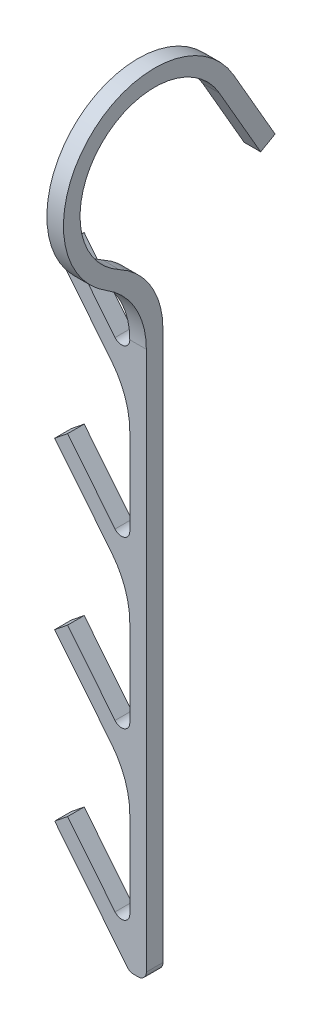
SolidWorks part; units mm, degrees
ref_plane "Front Plane" through (0, 0, 0) normal (0, 0, 1) x (1, 0, 0)
ref_plane "Top Plane" through (0, 0, 0) normal (0, 1, 0) x (1, 0, 0)
ref_plane "Right Plane" through (0, 0, 0) normal (1, 0, 0) x (0, 0, -1)
sketch "Sketch1" plane through (0, 0, 0) normal (1, 0, 0) x (0, 0, -1)
  circle A2 centre (0, 0) radius 22
  circle A3 centre (0, 0) radius 18
  dimension "D1" = 44
  dimension "D2" = 4
extrude "Boss-Extrude1" add sketch "Sketch1" along normal blind 4
sketch "Sketch2" plane through (4, 0, 0) normal (1, 0, 0) x (0, 0, -1)
  line L0 (19.0526, 11) -> (29.0526, -6.3205)
  line L1 (29.0526, -6.3205) -> (25.5885, -8.3205)
  line L2 (25.5885, -8.3205) -> (15.5885, 9)
  line L3 (15.5885, 9) -> (19.0526, 11)
  line L4 (0, 0) -> (0, 18) construction
  circle A0 centre (0, 0) radius 22 construction
  circle A1 centre (0, 0) radius 18 construction
  dimension "D1" = 20
  dimension "D2" = 30
extrude "Boss-Extrude2" add sketch "Sketch2" against normal up to surface (4 mm away) up to face at (0, 0, -22)
sketch "Sketch3" plane through (4, 0, 0) normal (1, 0, 0) x (0, 0, -1)
  line L0 (4.6587, -17.3867) -> (5.694, -21.2504)
  line L1 (0, 0) -> (0, -22) construction
  line L2 (21.913, -1.9545) -> (15.5885, 9)
  line L3 (21.913, -1.9545) -> (25.5885, -8.3205) construction
  circle A0 centre (0, 0) radius 18
  circle A1 centre (0, 0) radius 22
  circle A2 centre (0, 0) radius 18 construction
  arc A3 (19.0526, 11) -> (21.913, -1.9545) centre (0, 0) ccw construction
  circle M6 centre (0, 0) radius 18
  arc M8 (19.0526, 11) -> (21.913, -1.9545) centre (0, 0) ccw
  dimension "D1" = 15
extrude "Cut-Extrude1" cut sketch "Sketch3" against normal through all contours L2 L0 M8 M6 region at (4, -10.4169, -15.0287)
sketch "Sketch4" plane through (4, 0, 0) normal (1, 0, 0) x (0, 0, -1)
  line L1 (-2, -17.8885) -> (2, -17.8885)
  line L2 (-2, -17.8885) -> (-2, -47.8885)
  line L3 (-2, -47.8885) -> (2, -47.8885)
  line L4 (2, -17.8885) -> (2, -47.8885)
  arc A0 (15.5885, 9) -> (4.6587, -17.3867) centre (0, 0) ccw construction
  point P7 (0, -17.8885)
  dimension "D1" = 4
  dimension "D2" = 30
extrude "Boss-Extrude3" add sketch "Sketch4" against normal up to surface (4 mm away) up to face at (0, -1.442, -6.6971)
sketch "Sketch5" plane through (4, 0, 0) normal (1, 0, 0) x (0, 0, -1)
  line L0 (2, -21.9089) -> (2, -17.8885)
  line L1 (2, -17.8885) -> (4.6587, -17.3867)
  line L2 (4.6587, -17.3867) -> (5.694, -21.2504)
  arc A0 (2, -21.9089) -> (5.694, -21.2504) centre (2, -11.2189) ccw
extrude "Cut-Extrude2" cut sketch "Sketch5" against normal through all
fillet "Fillet1" radius 20 2 edges at (2, -17.8885, -2) (2, -21.9089, 2)
fillet "Fillet2" radius 20 1 edges at (2, -17.8885, 2)
sketch "Sketch6" plane through (0, 0, 0) normal (-1, 0, 0) x (0, 0, 1)
  line L0 (-2, -47.8885) -> (2, -47.8885) construction
  line L1 (-2, -47.8885) -> (2, -47.8885)
  line L2 (-2, -47.8885) -> (-2, -167.8885)
  line L3 (-2, -167.8885) -> (2, -167.8885)
  line L4 (2, -47.8885) -> (2, -167.8885)
  point P4 (0, -47.8885)
  point P7 (0, -47.8885)
  dimension "D1" = 120
  dimension "D2" = 4
extrude "Boss-Extrude4" add sketch "Sketch6" against normal up to surface (4 mm away) up to face at (4, -15.5959, -3.8329)
sketch "Sketch7" plane through (0, 0, 2) normal (0, 0, 1) x (1, 0, 0)
  line L0 (0, -167.8885) -> (-18.1152, -145.3977)
  line L1 (0, -167.8885) -> (0, -35.7771) construction
  line L2 (-18.1152, -145.3977) -> (-15, -142.8885)
  line L3 (-15, -142.8885) -> (0, -161.5118)
  line L4 (0, -161.5118) -> (0, -167.8885)
  line L5 (0, -121.5118) -> (0, -127.8885)
  line L6 (0, -127.8885) -> (-18.1152, -105.3977)
  line L7 (-18.1152, -105.3977) -> (-15, -102.8885)
  line L8 (-15, -102.8885) -> (0, -121.5118)
  line L9 (0, -81.5118) -> (0, -87.8885)
  line L10 (0, -87.8885) -> (-18.1152, -65.3977)
  line L11 (-18.1152, -65.3977) -> (-15, -62.8885)
  line L12 (-15, -62.8885) -> (0, -81.5118)
  line L13 (0, -41.5118) -> (0, -47.8885)
  line L14 (0, -47.8885) -> (-18.1152, -25.3977)
  line L15 (-18.1152, -25.3977) -> (-15, -22.8885)
  line L16 (-15, -22.8885) -> (0, -41.5118)
  dimension "D1" = 4
  dimension "D2" = 15
  dimension "D3" = 25
  dimension "D5" = 33.6232
  dimension "D4" = 4
extrude "Boss-Extrude5" add sketch "Sketch7" against normal up to surface (4 mm away) up to face at (2, -100.6775, -2)
fillet "Fillet3" radius 20 3 edges at (0, -127.8885, 0) (0, -87.8885, 0) (0, -47.8885, 0)
fillet "Fillet4" radius 2 2 edges at (0, -167.8885, 0) (4, -167.8885, 0)
fillet "Fillet5" radius 2 4 edges at (0, -161.5118, 0) (0, -121.5118, 0) (0, -81.5118, 0) (0, -41.5118, 0)
